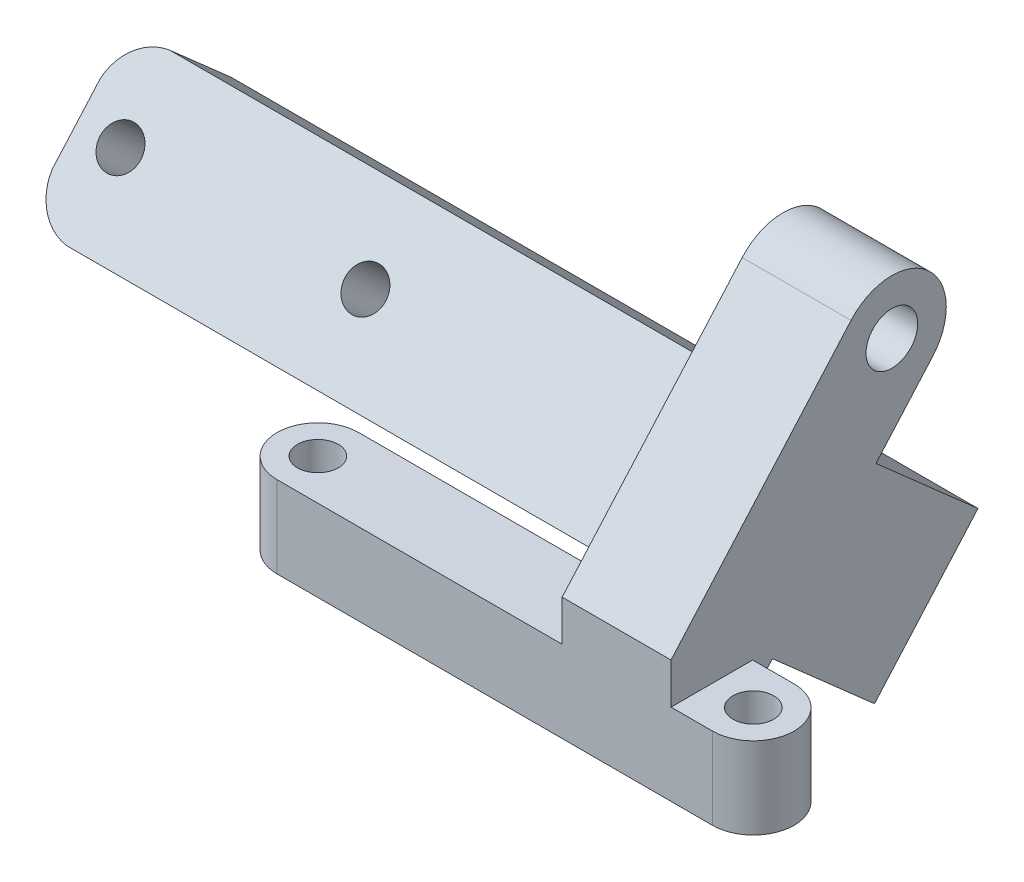
SolidWorks part; units mm, degrees
ref_plane "前基準面" through (0, 0, 0) normal (0, 0, 1) x (1, 0, 0)
ref_plane "上基準面" through (0, 0, 0) normal (0, 1, 0) x (1, 0, 0)
ref_plane "右基準面" through (0, 0, 0) normal (1, 0, 0) x (0, 0, -1)
sketch "草圖1" plane through (0, 0, 0) normal (0, 1, 0) x (1, 0, 0)
  line L0 (-38.677, 0) -> (-6.677, 0) construction
  line L1 (-38.677, 3) -> (-6.677, 3)
  line L2 (-38.677, -3) -> (-6.677, -3)
  line L4 (-17.7228, 3) -> (-9.7228, 3)
  line L5 (-17.7228, 3) -> (-17.7228, -3)
  line L6 (-17.7228, -3) -> (-9.7228, -3)
  line L7 (-9.7228, 3) -> (-9.7228, -3)
  arc A0 (-38.677, 3) -> (-38.677, -3) centre (-38.677, 0) ccw
  arc A1 (-6.677, -3) -> (-6.677, 3) centre (-6.677, 0) ccw
  circle A2 centre (-6.677, 0) radius 1.5
  circle A3 centre (-38.677, 0) radius 1.5
  point P3 (-22.677, 0)
  dimension "D1" = 32
  dimension "D2" = 8
  dimension "D4" = 3
  dimension "D3" = 6
extrude "填料-伸長2" add sketch "草圖1" against normal blind 6 contours A3 L5 L1 A0 L2 | L5 L0 L7 L1 | L0 L5 L2 L7 | L2 A1 L1 L7 A2 region at (-17.9697, 0, 1.5) region at (-13.7228, 0, -1.5) region at (-13.7228, 0, 1.5) region at (-9.6376, 0, -1.5)
extrude "填料-伸長3" add sketch "草圖1<4>" along normal blind 3 contours L0 L5 L2 L7 | L5 L0 L7 L1 region at (-13.7228, 0, -1.5) region at (-13.7228, 0, 1.5)
sketch "草圖1<4>" plane through (0, 0, 0) normal (0, 1, 0) x (1, 0, 0) same geometry as "草圖1"
sketch "草圖3" plane through (-9.7228, 0, 0) normal (1, 0, 0) x (0, 0, -1)
  line L0 (-3, 3) -> (-3, 0) construction
  line L2 (-3, 2.6558) -> (-3, 0)
  line L3 (13.2288, 15.3542) -> (0, 0.3542) construction
  line L4 (3, -6) -> (3, 0) construction
  line L5 (16.2288, 12.7085) -> (10.2288, 18)
  line L6 (16.2288, 12.7085) -> (3, -2.2915)
  line L7 (10.2288, 18) -> (-3, 3)
  line L8 (3, -2.2915) -> (-3, 3)
  line L9 (16.2288, 12.7085) -> (3, -2.2915)
  line L10 (10.2288, 18) -> (-3, 3)
  arc A0 (16.2288, 12.7085) -> (10.2288, 18) centre (13.2288, 15.3542) ccw
  arc A1 (-3, 3) -> (3, -2.2915) centre (0, 0.3542) ccw
  point P15 (6.6144, 7.8542)
  dimension "D1" = 8
  dimension "D2" = 20
extrude "填料-伸長28" add sketch "草圖3" against normal blind 8 contours L5 A0 | L5 L7 L8 L6 region at (-9.7228, 16.6275, -14.3516)
sketch "草圖4" plane through (0, -2.4908, -2.8243) normal (0, -0.6614, -0.75) x (-1, 0, 0)
  line L0 (9.7228, 13.9612) -> (9.7228, 2.4612)
  line L1 (9.7228, 13.9612) -> (17.6833, 13.9612)
  line L2 (9.7228, 2.4612) -> (17.6833, 2.4612)
  line L3 (17.6833, 13.9612) -> (17.6833, 2.4612)
  dimension "D1" = 11.5
extrude "填料-伸長29" add sketch "草圖4" along normal blind 10
sketch "草圖6" plane through (-17.6833, 0, 0) normal (-1, 0, 0) x (0, 0, 1)
  line L0 (-19.5587, 1.3657) -> (-11.9522, -7.2593)
  line L1 (-19.5587, 1.3657) -> (-15.0587, 5.3344)
  line L2 (-11.9522, -7.2593) -> (-7.4522, -3.2906)
  line L3 (-15.0587, 5.3344) -> (-7.4522, -3.2906)
  line L4 (-11.9522, -7.2593) -> (-19.5587, 1.3657) construction
  line L5 (-19.5587, 1.3657) -> (-12.0587, 7.9801) construction
  dimension "D1" = 6
extrude "填料-伸長30" add sketch "草圖6" along normal blind 50 contours L0 L1 L3 L2
sketch "草圖7" plane through (0, -9.1051, -10.3243) normal (0, -0.6614, -0.75) x (-1, 0, 0)
  line L0 (67.6833, 2.4612) -> (67.6833, 5.5409)
  line L1 (63.8434, 13.9612) -> (67.6833, 13.9612)
  line L2 (67.6833, 13.9612) -> (9.7228, 13.9612) construction
  line L3 (67.6833, 13.9612) -> (67.6833, 10.8815)
  line L4 (67.6833, 13.9612) -> (67.6833, 2.4612) construction
  line L5 (67.6833, 8.2112) -> (55.4337, 8.2112) construction
  line L6 (63.8434, 2.4612) -> (67.6833, 2.4612)
  circle A0 centre (64.4806, 8.278) radius 1.5
  circle A1 centre (46.4806, 8.278) radius 1.5
  arc A2 (67.6833, 10.8815) -> (63.8434, 13.9612) centre (64.2235, 10.5014) ccw
  arc A3 (67.6833, 5.5409) -> (63.8434, 2.4612) centre (64.2235, 5.921) cw
  line M2 (67.6833, 13.9612) -> (9.7228, 13.9612)
  line M5 (67.6833, 2.4612) -> (67.6833, 13.9612)
  dimension "D1" = 3
  dimension "D2" = 3
  dimension "D3" = 18
extrude "除料-伸長1" cut sketch "草圖7" against normal blind 10 contours A0 | A0 L5 | A2 M5 M2 | A3 L6 M5 | A1 region at (-66.9287, -6.6933, -12.4513) region at (-64.4806, -3.4013, -15.3546) region at (-64.4806, -2.4461, -16.197) region at (-66.9287, 0.7998, -19.0596)
sketch "草圖8" plane through (-9.7228, 0, 0) normal (1, 0, 0) x (0, 0, -1)
  circle A0 centre (13.2288, 15.3542) radius 1.9
  dimension "D1" = 3.8
extrude "除料-伸長2" cut sketch "草圖8" against normal blind 19 contours A0
